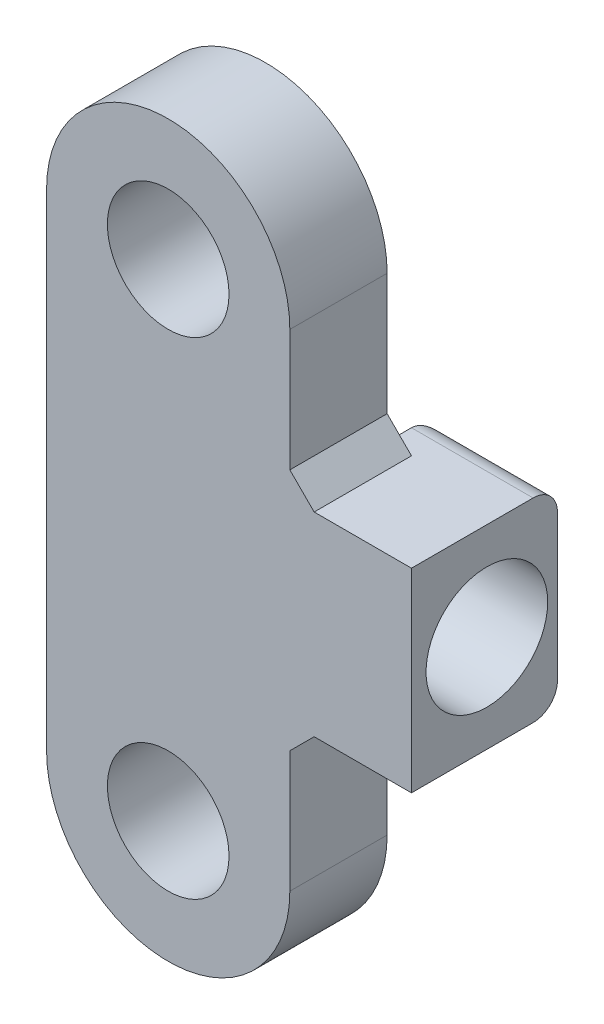
SolidWorks part; units mm, degrees
material "ABS"
ref_plane "前视基准面" through (0, 0, 0) normal (0, 0, 1) x (1, 0, 0)
ref_plane "上视基准面" through (0, 0, 0) normal (0, 1, 0) x (1, 0, 0)
ref_plane "右视基准面" through (0, 0, 0) normal (1, 0, 0) x (0, 0, -1)
other "Configuration Table"
sketch "草图1" plane through (0, 0, 0) normal (0, 0, 1) x (1, 0, 0)
  line L0 (0, 10) -> (0, -10) construction
  line L1 (5, 10) -> (5, -10)
  line L2 (-5, 10) -> (-5, -10)
  arc A0 (5, 10) -> (-5, 10) centre (0, 10) ccw
  arc A1 (-5, -10) -> (5, -10) centre (0, -10) ccw
  circle A2 centre (0, 10) radius 2.5
  circle A3 centre (0, -10) radius 2.5
  circle A4 centre (0, 10) radius 4 construction
  point P2 (0, 0)
  dimension "D3" = 5
  dimension "D4" = 8
  dimension "D1" = 20
  dimension "D2" = 10
extrude "凸台-拉伸1" add sketch "草图1" along normal blind 4 contours L2 A1 L1 A0 A3 A2 | L1 region at (0, 0, 0)
sketch "草图2" plane through (5, 0, 0) normal (1, 0, 0) x (0, 0, -1)
  line L0 (-4, 0) -> (-0.9, 0) construction
  line L2 (-4, 10) -> (-4, -10) construction
  line L8 (-4, 4) -> (2, 4)
  line L9 (-4, 4) -> (-4, -4)
  line L10 (-4, -4) -> (2, -4)
  line L11 (2, 4) -> (2, -4)
  line L13 (-4, 10) -> (-4, -10) construction
  line L14 (0, 10) -> (0, -10) construction
  circle A1 centre (-0.9, 0) radius 2.5
  dimension "D1" = 2
  dimension "D4" = 5
  dimension "D2" = 3.1
  dimension "D3" = 8
extrude "凸台-拉伸2" add sketch "草图2" along normal blind 5
chamfer "倒角1" distance 1 angle 45 2 edges at (5, -4, 2) (5, 4, 2)
fillet "圆角1" radius 1 3 edges at (7.5, -4, -2) (7.5, 4, -2) (5, 0, -2)
